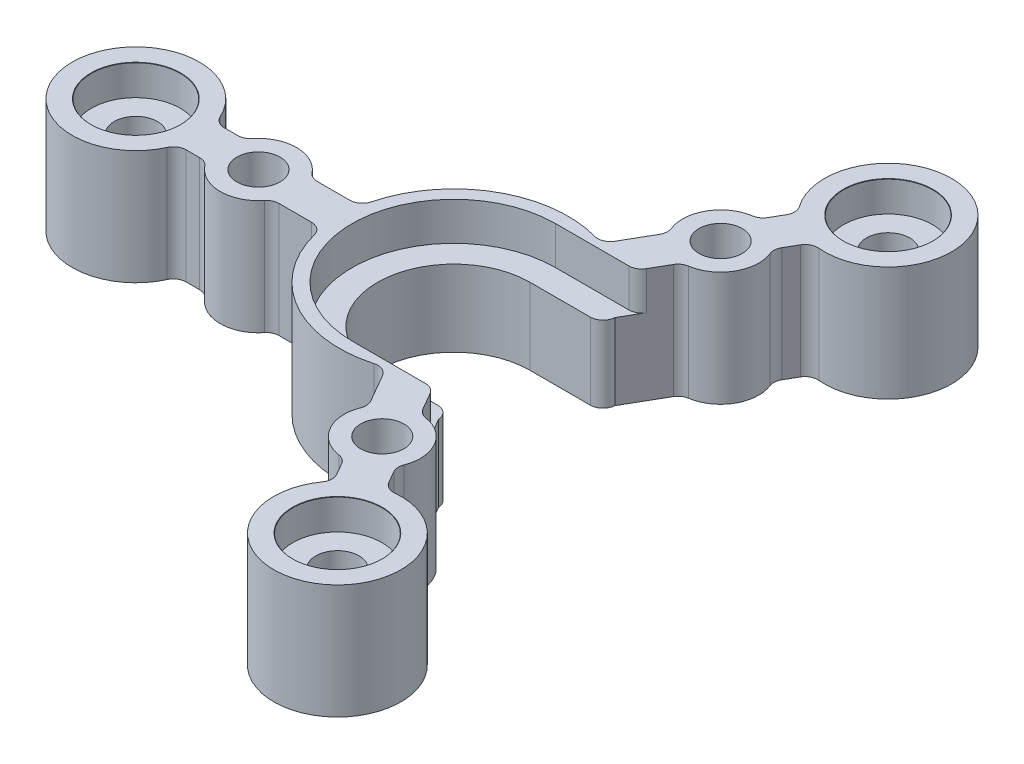
SolidWorks part; units mm, degrees
ref_plane "Front Plane" through (0, 0, 0) normal (0, 0, 1) x (1, 0, 0)
ref_plane "Top Plane" through (0, 0, 0) normal (0, 1, 0) x (1, 0, 0)
ref_plane "Right Plane" through (0, 0, 0) normal (1, 0, 0) x (0, 0, -1)
sketch "Sketch1" plane through (0, 0, 0) normal (0, 1, 0) x (1, 0, 0)
  line L0 (10.2781, 14.8022) -> (7.68, 16.3022)
  line L1 (-12.7619, 1.5) -> (-5.8095, 1.5)
  line L2 (-12.7619, 1.5) -> (-12.7619, -1.5)
  line L3 (-12.7619, -1.5) -> (-5.8095, -1.5)
  line L4 (-5.8095, 1.5) -> (-5.8095, -1.5)
  line L5 (-12.7619, 1.5) -> (-5.8095, -1.5) construction
  line L6 (-12.7619, -1.5) -> (-5.8095, 1.5) construction
  line L7 (-17.9581, 1.5) -> (-20.2303, 1.5)
  line L8 (-17.9581, 1.5) -> (-17.9581, -1.5)
  line L9 (-17.9581, -1.5) -> (-20.2303, -1.5)
  line L10 (-20.2303, 1.5) -> (-20.2303, -1.5)
  line L11 (-17.9581, 1.5) -> (-20.2303, -1.5) construction
  line L12 (-17.9581, -1.5) -> (-20.2303, 1.5) construction
  line L13 (10.2781, 14.8022) -> (11.4142, 16.77)
  line L14 (11.4142, 16.77) -> (8.8161, 18.27)
  line L15 (7.68, 16.3022) -> (8.8161, 18.27)
  line L16 (7.68, 10.3022) -> (5.0819, 11.8022)
  line L17 (7.68, 10.3022) -> (4.2038, 4.2812)
  line L18 (4.2038, 4.2812) -> (1.6057, 5.7812)
  line L19 (5.0819, 11.8022) -> (1.6057, 5.7812)
  line L20 (7.68, -16.3022) -> (10.2781, -14.8022)
  line L21 (7.68, -16.3022) -> (8.8161, -18.27)
  line L22 (8.8161, -18.27) -> (11.4142, -16.77)
  line L23 (10.2781, -14.8022) -> (11.4142, -16.77)
  line L24 (5.0819, -11.8022) -> (7.68, -10.3022)
  line L25 (5.0819, -11.8022) -> (1.6057, -5.7812)
  line L26 (1.6057, -5.7812) -> (4.2038, -4.2812)
  line L27 (7.68, -10.3022) -> (4.2038, -4.2812)
  circle A0 centre (0, 0) radius 6
  circle A1 centre (0, 0) radius 25 construction
  circle A2 centre (0, 0) radius 15.36 construction
  circle A3 centre (-15.36, 0) radius 3
  circle A4 centre (-25, 0) radius 5
  circle A5 centre (12.5, 21.6506) radius 5
  circle A6 centre (7.68, 13.3022) radius 3
  circle A7 centre (12.5, -21.6506) radius 5
  circle A8 centre (7.68, -13.3022) radius 3
  circle A9 centre (0, 0) radius 9
  point P13 (-9.2857, 0)
  point P16 (-12.7619, 0)
  point P21 (-19.0942, 0)
  point P47 (0, 0)
  dimension "D1" = 12
  dimension "D2" = 50
  dimension "D3" = 30.72
  dimension "D4" = 6
  dimension "D5" = 10
  dimension "D8" = 18
  dimension "D6" = 3
  dimension "D7" = 3
extrude "Boss-Extrude1" add sketch "Sketch1" along normal blind 6 contours L3 A9 L25 A0 | L1 A9 L3 A0 | L19 A9 L1 A0 | L17 A9 L19 A0 | L27 A9 L17 A0 | L25 A9 L27 A0 | A9 L1 A3 L3 | L2 A3 L8 | L8 A3 | A4 L9 A3 L7 | L10 A4 | L10 A4 | A9 L25 A8 L27 | L20 A8 L24 | L24 A8 | L20 A8 | A8 L21 A7 L23 | L22 A7 | L22 A7 | L2 A3 | A9 L17 A6 L19 | L16 A6 | L16 A6 L0 | L0 A6 | A6 L13 A5 L15 | L14 A5 | L14 A5 region at (7.68, 0, -13.3022) region at (9.5752, 0, -16.5847) region at (9.0599, 0, -15.6922) region at (10.069, 0, -17.44) region at (12.5144, 0, -21.6756) region at (5.363, 0, -9.2889) region at (6.3001, 0, -10.9121) region at (3.7236, 0, -6.4495) region at (-3.37, 0, -5.837) region at (6.7399, 0, 0) region at (-10.726, 0, 0) region at (-7.4472, 0, 0) region at (-12.6002, 0, 0) region at (-15.36, 0, 0) region at (-3.37, 0, 5.837) region at (3.7236, 0, 6.4495) region at (5.363, 0, 9.2889) region at (-19.1504, 0, 0) region at (-18.1198, 0, 0) region at (7.68, 0, 13.3022) region at (6.3001, 0, 10.9121) region at (-20.138, 0, 0) region at (-25.0288, 0, 0) region at (9.5752, 0, 16.5847) region at (9.0599, 0, 15.6922) region at (10.069, 0, 17.44) region at (12.5144, 0, 21.6756)
sketch "Sketch2" plane through (0, 6, 0) normal (0, 1, 0) x (1, 0, 0)
  line L1 (0, 6) -> (9, 6)
  line L2 (0, 6) -> (0, -6)
  line L3 (0, -6) -> (9, -6)
  line L4 (9, 6) -> (9, -6)
  line L5 (0, 6) -> (9, -6) construction
  line L6 (0, -6) -> (9, 6) construction
  circle A0 centre (0, 0) radius 6 construction
  circle A1 centre (0, 0) radius 6
  arc A2 (5.7361, -6.9352) -> (5.7361, 6.9352) centre (0, 0) ccw construction
  point P7 (4.5, 0)
  point P11 (0, -4.6214)
  circle M6 centre (0, 0) radius 6
  arc M17 (5.7361, -6.9352) -> (5.7361, 6.9352) centre (0, 0) ccw
extrude "Cut-Extrude1" cut sketch "Sketch2" against normal blind 10 contours L3 L1 M6 M17 region at (6.3072, 6, 0)
sketch "Sketch3" plane through (0, 6, 0) normal (0, 1, 0) x (1, 0, 0)
  line L1 (0, 8) -> (8, 8)
  line L2 (0, 8) -> (0, -8)
  line L3 (0, -8) -> (8, -8)
  line L4 (8, 8) -> (8, -8)
  line L5 (0, 8) -> (8, -8) construction
  line L6 (0, -8) -> (8, 8) construction
  line L14 (0, 6) -> (6.7082, 6)
  line L15 (5.7361, 6.9352) -> (7.68, 10.3022)
  line L16 (10.2781, 14.8022) -> (11.4142, 16.77)
  line L17 (8.8161, 18.27) -> (7.68, 16.3022)
  line L18 (5.0819, 11.8022) -> (3.138, 8.4352)
  line L19 (-8.8741, 1.5) -> (-12.7619, 1.5)
  line L20 (-17.9581, 1.5) -> (-20.2303, 1.5)
  line L21 (-20.2303, -1.5) -> (-17.9581, -1.5)
  line L22 (-12.7619, -1.5) -> (-8.8741, -1.5)
  line L23 (3.138, -8.4352) -> (5.0819, -11.8022)
  line L24 (7.68, -16.3022) -> (8.8161, -18.27)
  line L25 (11.4142, -16.77) -> (10.2781, -14.8022)
  line L26 (7.68, -10.3022) -> (5.7361, -6.9352)
  line L27 (6.7082, -6) -> (0, -6)
  line L28 (0, 6) -> (6.7082, 6)
  line L29 (5.7361, 6.9352) -> (7.68, 10.3022)
  line L30 (10.2781, 14.8022) -> (11.4142, 16.77)
  line L31 (8.8161, 18.27) -> (7.68, 16.3022)
  line L32 (5.0819, 11.8022) -> (3.138, 8.4352)
  line L33 (-8.8741, 1.5) -> (-12.7619, 1.5)
  line L34 (-17.9581, 1.5) -> (-20.2303, 1.5)
  line L35 (-20.2303, -1.5) -> (-17.9581, -1.5)
  line L36 (-12.7619, -1.5) -> (-8.8741, -1.5)
  line L37 (3.138, -8.4352) -> (5.0819, -11.8022)
  line L38 (7.68, -16.3022) -> (8.8161, -18.27)
  line L39 (11.4142, -16.77) -> (10.2781, -14.8022)
  line L40 (7.68, -10.3022) -> (5.7361, -6.9352)
  line L41 (6.7082, -6) -> (0, -6)
  circle A0 centre (0, 0) radius 8
  arc A14 (0, 6) -> (0, -6) centre (0, 0) ccw
  arc A15 (6.7082, 6) -> (5.7361, 6.9352) centre (0, 0) ccw
  arc A16 (7.68, 10.3022) -> (10.2781, 14.8022) centre (7.68, 13.3022) ccw
  arc A17 (11.4142, 16.77) -> (8.8161, 18.27) centre (12.5, 21.6506) ccw
  arc A18 (7.68, 16.3022) -> (5.0819, 11.8022) centre (7.68, 13.3022) ccw
  arc A19 (3.138, 8.4352) -> (-8.8741, 1.5) centre (0, 0) ccw
  arc A20 (-12.7619, 1.5) -> (-17.9581, 1.5) centre (-15.36, 0) ccw
  arc A21 (-20.2303, 1.5) -> (-20.2303, -1.5) centre (-25, 0) ccw
  arc A22 (-17.9581, -1.5) -> (-12.7619, -1.5) centre (-15.36, 0) ccw
  arc A23 (-8.8741, -1.5) -> (3.138, -8.4352) centre (0, 0) ccw
  arc A24 (5.0819, -11.8022) -> (7.68, -16.3022) centre (7.68, -13.3022) ccw
  arc A25 (8.8161, -18.27) -> (11.4142, -16.77) centre (12.5, -21.6506) ccw
  arc A26 (10.2781, -14.8022) -> (7.68, -10.3022) centre (7.68, -13.3022) ccw
  arc A27 (5.7361, -6.9352) -> (6.7082, -6) centre (0, 0) ccw
  arc A28 (0, 6) -> (0, -6) centre (0, 0) ccw
  arc A29 (6.7082, 6) -> (5.7361, 6.9352) centre (0, 0) ccw
  arc A30 (7.68, 10.3022) -> (10.2781, 14.8022) centre (7.68, 13.3022) ccw
  arc A31 (11.4142, 16.77) -> (8.8161, 18.27) centre (12.5, 21.6506) ccw
  arc A32 (7.68, 16.3022) -> (5.0819, 11.8022) centre (7.68, 13.3022) ccw
  arc A33 (3.138, 8.4352) -> (-8.8741, 1.5) centre (0, 0) ccw
  arc A34 (-12.7619, 1.5) -> (-17.9581, 1.5) centre (-15.36, 0) ccw
  arc A35 (-20.2303, 1.5) -> (-20.2303, -1.5) centre (-25, 0) ccw
  arc A36 (-17.9581, -1.5) -> (-12.7619, -1.5) centre (-15.36, 0) ccw
  arc A37 (-8.8741, -1.5) -> (3.138, -8.4352) centre (0, 0) ccw
  arc A38 (5.0819, -11.8022) -> (7.68, -16.3022) centre (7.68, -13.3022) ccw
  arc A39 (8.8161, -18.27) -> (11.4142, -16.77) centre (12.5, -21.6506) ccw
  arc A40 (10.2781, -14.8022) -> (7.68, -10.3022) centre (7.68, -13.3022) ccw
  arc A41 (5.7361, -6.9352) -> (6.7082, -6) centre (0, 0) ccw
  point P25 (4, 0)
  line M32 (5.7361, 6.9352) -> (7.68, 10.3022)
  arc M33 (7.68, 10.3022) -> (10.2781, 14.8022) centre (7.68, 13.3022) ccw
  line M34 (10.2781, 14.8022) -> (11.4142, 16.77)
  arc M35 (11.4142, 16.77) -> (8.8161, 18.27) centre (12.5, 21.6506) ccw
  line M36 (8.8161, 18.27) -> (7.68, 16.3022)
  arc M37 (7.68, 16.3022) -> (5.0819, 11.8022) centre (7.68, 13.3022) ccw
  line M38 (5.0819, 11.8022) -> (3.138, 8.4352)
  arc M39 (3.138, 8.4352) -> (-8.8741, 1.5) centre (0, 0) ccw
  line M40 (-8.8741, 1.5) -> (-12.7619, 1.5)
  arc M41 (-12.7619, 1.5) -> (-17.9581, 1.5) centre (-15.36, 0) ccw
  line M42 (-17.9581, 1.5) -> (-20.2303, 1.5)
  arc M43 (-20.2303, 1.5) -> (-20.2303, -1.5) centre (-25, 0) ccw
  line M44 (-20.2303, -1.5) -> (-17.9581, -1.5)
  arc M45 (-17.9581, -1.5) -> (-12.7619, -1.5) centre (-15.36, 0) ccw
  line M46 (-12.7619, -1.5) -> (-8.8741, -1.5)
  arc M47 (-8.8741, -1.5) -> (3.138, -8.4352) centre (0, 0) ccw
  line M48 (3.138, -8.4352) -> (5.0819, -11.8022)
  arc M49 (5.0819, -11.8022) -> (7.68, -16.3022) centre (7.68, -13.3022) ccw
  line M50 (7.68, -16.3022) -> (8.8161, -18.27)
  arc M51 (8.8161, -18.27) -> (11.4142, -16.77) centre (12.5, -21.6506) ccw
  line M52 (11.4142, -16.77) -> (10.2781, -14.8022)
  arc M53 (10.2781, -14.8022) -> (7.68, -10.3022) centre (7.68, -13.3022) ccw
  line M54 (7.68, -10.3022) -> (5.7361, -6.9352)
  dimension "D2" = 16
  dimension "D1" = 0
extrude "Boss-Extrude2" add sketch "Sketch3" along normal blind 3 contours A0 L1 L3 M32 M33 M34 M35 M36 M37 M38 M39 M40 M41 M42 M43 M44 M45 M46 M47 M48 M49 M50 M51 M52 M53 M54 region at (-8.714, 6, 0)
fillet "Fillet1" radius 1 26 edges at (7.68, 4.5, 10.3022) (10.2781, 4.5, 14.8022) (11.4142, 4.5, 16.77) (8.8161, 4.5, 18.27) (7.68, 4.5, 16.3022) (5.0819, 4.5, 11.8022) (3.138, 4.5, 8.4352) (-8.8741, 4.5, 1.5) (-12.7619, 4.5, 1.5) (-17.9581, 4.5, 1.5) (-20.2303, 4.5, 1.5) (-20.2303, 4.5, -1.5) (-17.9581, 4.5, -1.5) (-12.7619, 4.5, -1.5) (-8.8741, 4.5, -1.5) (3.138, 4.5, -8.4352) (5.0819, 4.5, -11.8022) (7.68, 4.5, -16.3022) (8.8161, 4.5, -18.27) (11.4142, 4.5, -16.77) (10.2781, 4.5, -14.8022) (7.68, 4.5, -10.3022) (6.3509, 7.5, -8) (6.3509, 7.5, 8) (6.7082, 3, 6) (6.7082, 3, -6)
hole_wizard "M3 Clearance Hole2" positions "Sketch6" profile "Sketch5" hole size "M3" standard "ANSI Metric" end condition through all
sketch "Sketch6" plane through (0, 9, 0) normal (0, 1, 0) x (1, 0, 0)
  arc A0 (8.1329, 10.3365) -> (10.4747, 14.3928) centre (7.68, 13.3022) ccw construction
  arc A1 (4.8853, -12.2115) -> (7.2271, -16.2678) centre (7.68, -13.3022) ccw construction
  arc A2 (-17.7019, -1.875) -> (-13.0181, -1.875) centre (-15.36, 0) ccw construction
  arc A3 (8.1329, 10.3365) -> (10.4747, 14.3928) centre (7.68, 13.3022) ccw
  arc A4 (4.8853, -12.2115) -> (7.2271, -16.2678) centre (7.68, -13.3022) ccw
  arc A5 (-17.7019, -1.875) -> (-13.0181, -1.875) centre (-15.36, 0) ccw
  point P1 (7.68, 13.3022)
  point P4 (7.68, -13.3022)
  point P7 (-15.36, 0)
sketch "Sketch5" plane through (7.68, 9, -13.3022) normal (1, 0, 0) x (0, 0, 1)
  line L0 (0, 0) -> (0, 9)
  line L1 (0, 9) -> (1.7, 9)
  line L2 (1.7, 9) -> (1.7, 0)
  line L5 (1.7, 0) -> (0, 0)
  line L11 (0, -6.35) -> (0, 107.95) construction
  dimension "Thru Hole Dia." = 3.4
  dimension "Thru Hole Depth" = 9
hole_wizard "CBORE for M3 Pan Head Machine Screw1" positions "Sketch7" profile "Sketch8" counterbore size "M3" standard "ANSI Metric" end condition through all
sketch "Sketch7" plane through (0, 9, 0) normal (0, 1, 0) x (1, 0, 0)
  arc A0 (12.0316, 16.6726) -> (8.4231, 18.756) centre (12.5, 21.6506) ccw construction
  arc A1 (8.4231, -18.756) -> (12.0316, -16.6726) centre (12.5, -21.6506) ccw construction
  arc A2 (-20.4547, 2.0833) -> (-20.4547, -2.0833) centre (-25, 0) ccw construction
  arc A3 (12.0316, 16.6726) -> (8.4231, 18.756) centre (12.5, 21.6506) ccw
  arc A4 (8.4231, -18.756) -> (12.0316, -16.6726) centre (12.5, -21.6506) ccw
  arc A5 (-20.4547, 2.0833) -> (-20.4547, -2.0833) centre (-25, 0) ccw
  point P1 (12.5, 21.6506)
  point P4 (12.5, -21.6506)
  point P7 (-25, 0)
sketch "Sketch8" plane through (12.5, 9, -21.6506) normal (1, 0, 0) x (0, 0, 1)
  line L0 (0, 0) -> (0, 9)
  line L1 (0, 9) -> (1.7, 9)
  line L3 (1.7, 9) -> (1.7, 2.4)
  line L4 (3.5, 2.4) -> (1.7, 2.4)
  line L5 (3.5, 2.4) -> (3.5, 0.025)
  line L6 (3.5, 0.025) -> (3.525, 0)
  line L7 (3.525, 0) -> (0, 0)
  line L8 (-3.5, 0.025) -> (-3.525, 0) construction
  line L11 (0, -6.35) -> (0, 107.95) construction
  dimension "Thru Hole Dia." = 3.4
  dimension "Thru Hole Depth" = 9
  dimension "C'Bore Dia." = 7
  dimension "C'Bore Depth" = 2.4
  dimension "Near C'Sink Dia." = 7.05
  dimension "Near C'Sink Angle" = 90
